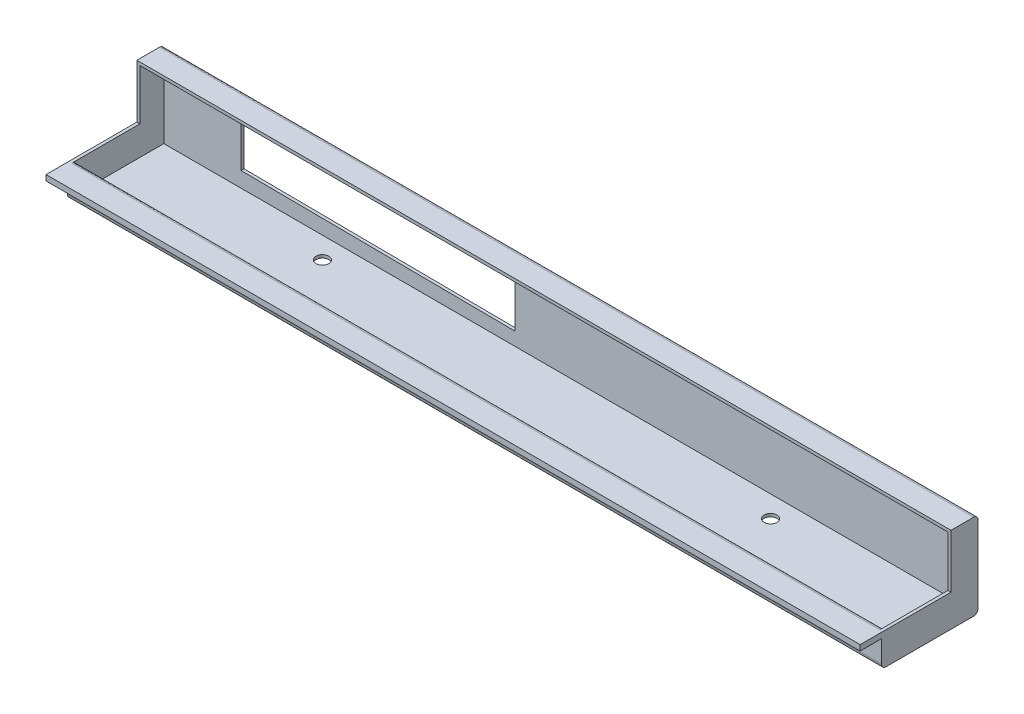
SolidWorks part; units mm, degrees
ref_plane "Front Plane" through (0, 0, 0) normal (0, 0, 1) x (1, 0, 0)
ref_plane "Top Plane" through (0, 0, 0) normal (0, 1, 0) x (1, 0, 0)
ref_plane "Right Plane" through (0, 0, 0) normal (1, 0, 0) x (0, 0, -1)
sketch "Sketch1" plane through (0, 0, 0) normal (0, 0, 1) x (1, 0, 0)
  line L1 (-241.3, -25.4) -> (241.3, -25.4)
  line L2 (-241.3, -25.4) -> (-241.3, 25.4)
  line L3 (-241.3, 25.4) -> (241.3, 25.4)
  line L4 (241.3, -25.4) -> (241.3, 25.4)
  line L5 (-241.3, -25.4) -> (241.3, 25.4) construction
  line L6 (-241.3, 25.4) -> (241.3, -25.4) construction
  point P0 (0, 0)
  dimension "D1" = 482.6
  dimension "D2" = 50.8
extrude "Boss-Extrude1" add sketch "Sketch1" along normal blind 69.85
sketch "Sketch2" plane through (0, 25.4, 0) normal (0, 1, 0) x (1, 0, 0)
  line L0 (241.3, -69.85) -> (241.3, 0) construction
  line L1 (-241.3, 0) -> (241.3, 0)
  line L2 (-241.3, 0) -> (-241.3, -16.002)
  line L3 (-241.3, -16.002) -> (241.3, -16.002)
  line L4 (241.3, 0) -> (241.3, -16.002)
  line L5 (-241.3, -34.925) -> (-219.8341, -34.925)
  line L6 (-241.3, -69.85) -> (-241.3, 0) construction
  line L7 (241.3, -69.85) -> (241.3, -53.848)
  line L8 (-241.3, -69.85) -> (-241.3, -53.848)
  line L9 (-241.3, -69.85) -> (241.3, -69.85)
  line L10 (-241.3, -53.848) -> (241.3, -53.848)
  line M6 (-241.3, 0) -> (-241.3, -69.85)
  line M8 (241.3, -69.85) -> (241.3, 0)
  dimension "D1" = 16.002
extrude "Cut-Extrude2" cut sketch "Sketch2" against normal blind 49.022 contours L10 L3 M6 M8 region at (0, 25.4, 34.925)
sketch "Sketch3" plane through (0, 25.4, 0) normal (0, 1, 0) x (1, 0, 0)
  line L1 (-241.3, -53.848) -> (241.3, -53.848)
  line L2 (-241.3, -53.848) -> (-241.3, -69.85)
  line L3 (-241.3, -69.85) -> (241.3, -69.85)
  line L4 (241.3, -53.848) -> (241.3, -69.85)
extrude "Cut-Extrude3" cut sketch "Sketch3" against normal blind 31.75
sketch "Sketch4" plane through (0, 0, 69.85) normal (0, 0, 1) x (1, 0, 0)
  line L0 (241.3, -25.4) -> (241.3, -6.35) construction
  line L1 (-241.3, -25.4) -> (241.3, -25.4)
  line L2 (-241.3, -25.4) -> (-241.3, -9.652)
  line L3 (-241.3, -9.652) -> (241.3, -9.652)
  line L4 (241.3, -25.4) -> (241.3, -9.652)
  line L5 (-241.3, -6.35) -> (241.3, -6.35) construction
  dimension "D1" = 3.302
extrude "Cut-Extrude4" cut sketch "Sketch4" against normal blind 12.7
shell "Shell2" thickness 1.778 removed face at (0, 0.889, 16.002)
sketch "Sketch5" plane through (0, 0, 53.848) normal (0, 0, -1) x (-1, 0, 0)
  line L0 (-241.3, -6.35) -> (241.3, -6.35) construction
  line L1 (241.3, -23.622) -> (239.522, -23.622)
  line L2 (241.3, -23.622) -> (241.3, -6.35)
  line L3 (241.3, -6.35) -> (239.522, -6.35)
  line L4 (239.522, -23.622) -> (239.522, -6.35)
  line L5 (0, -23.622) -> (0, -9.0933)
  line L6 (241.3, -23.622) -> (-241.3, -23.622) construction
  line L7 (-239.522, -23.622) -> (-239.522, -6.35)
  line L8 (-241.3, -6.35) -> (-239.522, -6.35)
  line L9 (-241.3, -23.622) -> (-241.3, -6.35)
  line L10 (-241.3, -23.622) -> (-239.522, -23.622)
  line M2 (241.3, -6.35) -> (-241.3, -6.35)
  line M4 (-241.3, -23.622) -> (241.3, -23.622)
  line M5 (241.3, -23.622) -> (241.3, -6.35)
  dimension "D1" = 1.778
extrude "Boss-Extrude2" add sketch "Sketch5" along normal blind 44.45 contours L4 M4 M5 M2 | L7 L8 L9 L10 region at (-240.411, -14.986, 53.848)
fillet "Fillet1" radius 2.54 4 edges at (0, -6.35, 53.848) (0, -25.4, 57.15) (0, -25.4, 0) (0, 25.4, 0)
sketch "Sketch6" plane through (0, -23.622, 0) normal (0, 1, 0) x (1, 0, 0)
  line L0 (-239.522, -1.778) -> (-239.522, -14.478)
  line L1 (-239.522, -53.848) -> (-239.522, -1.778) construction
  line L2 (-239.522, -14.478) -> (-132.842, -14.478)
  line L3 (0, -1.778) -> (0, -14.478)
  line L4 (-239.522, -1.778) -> (239.522, -1.778) construction
  circle A0 centre (-132.842, -14.478) radius 3.81
  circle A1 centre (132.842, -14.478) radius 3.81
  dimension "D1" = 12.7
  dimension "D2" = 106.68
extrude "Cut-Extrude5" cut sketch "Sketch6" against normal blind 44.45 contours A0 | A1 region at (-132.842, -23.622, 18.1802)
sketch "Sketch8" plane through (0, 0, 0) normal (0, 0, -1) x (-1, 0, 0)
  line L0 (31.482, 13.4) -> (31.482, -15.81)
  line L1 (31.482, -15.81) -> (193.8369, -14.5511)
  line L2 (193.8369, -14.5511) -> (193.8369, 13.4)
  line L3 (193.8369, 13.4) -> (31.482, 13.4)
extrude "Cut-Extrude6" cut sketch "Sketch8" against normal up to next
